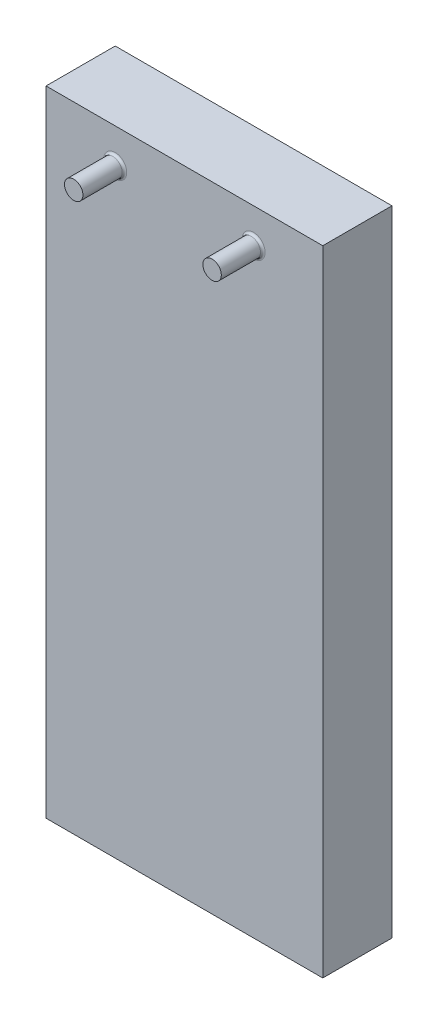
SolidWorks part; units mm, degrees
ref_plane "Front Plane" through (0, 0, 0) normal (0, 0, 1) x (1, 0, 0)
ref_plane "Top Plane" through (0, 0, 0) normal (0, 1, 0) x (1, 0, 0)
ref_plane "Right Plane" through (0, 0, 0) normal (1, 0, 0) x (0, 0, -1)
sketch "Sketch1" plane through (0, 0, 0) normal (0, 1, 0) x (1, 0, 0)
  line L1 (-60, -15) -> (60, -15)
  line L2 (-60, -15) -> (-60, 15)
  line L3 (-60, 15) -> (60, 15)
  line L4 (60, -15) -> (60, 15)
  line L5 (-60, -15) -> (60, 15) construction
  line L6 (-60, 15) -> (60, -15) construction
  point P0 (0, 0)
  dimension "D1" = 120
  dimension "D2" = 30
extrude "Boss-Extrude1" add sketch "Sketch1" along normal blind 275
sketch "Sketch2" plane through (0, 0, 15) normal (0, 0, 1) x (1, 0, 0)
  line L0 (-60, 245) -> (60, 245)
  line L1 (-60, 275) -> (-60, 0) construction
  line L2 (60, 275) -> (60, 0) construction
  line L3 (-60, 275) -> (60, 275) construction
  line L4 (-60, 245) -> (-60, 275)
  line L5 (-60, 260) -> (60, 260) construction
  circle A2 centre (-30, 260) radius 4
  circle A3 centre (30, 260) radius 4
  dimension "D4" = 8
  dimension "D1" = 30
  dimension "D2" = 30
  dimension "D3" = 30
extrude "Boss-Extrude2" add sketch "Sketch2" along normal blind 18 contours L5 A3 | A3 L5 | L5 A2 | A2 L5 region at (-30, 261.6977, 15) region at (30, 261.6977, 15) region at (30, 258.3023, 15) region at (-30, 258.3023, 15)
fillet "Fillet1" radius 1 2 edges at (26, 260, 15) (-34, 260, 15)
